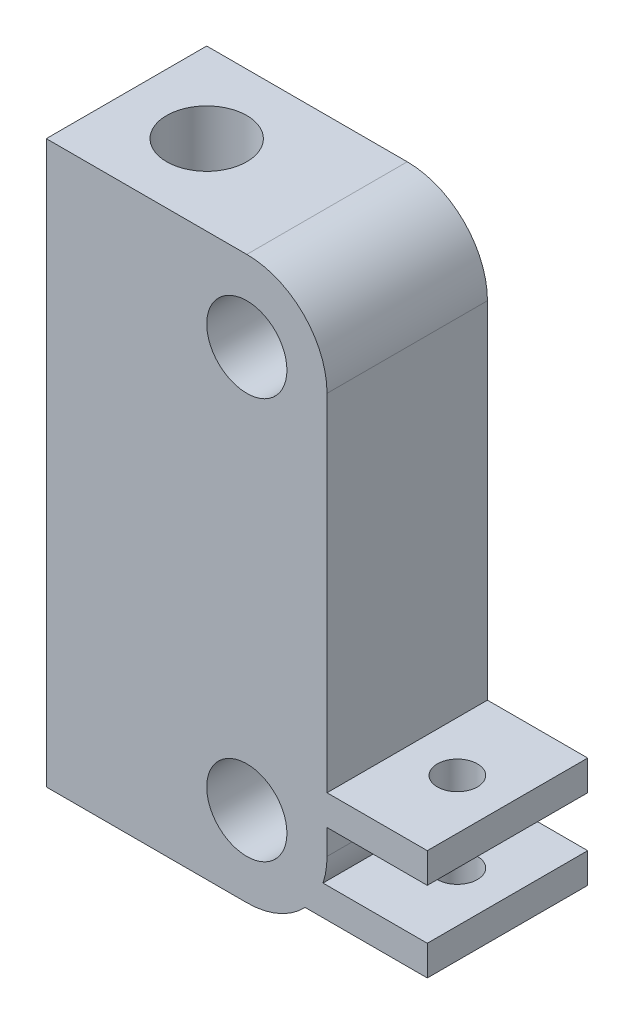
SolidWorks part; units mm, degrees
material "ABS"
ref_plane "Front Plane" through (0, 0, 0) normal (0, 0, 1) x (1, 0, 0)
ref_plane "Top Plane" through (0, 0, 0) normal (0, 1, 0) x (1, 0, 0)
ref_plane "Right Plane" through (0, 0, 0) normal (1, 0, 0) x (0, 0, -1)
sketch "Sketch1" plane through (0, 0, 0) normal (0, 0, 1) x (1, 0, 0)
  line L0 (11.942, -20.8688) -> (21.942, -20.8688)
  line L1 (-16.058, 21.6312) -> (3.942, 21.6312)
  line L2 (-16.058, 21.6312) -> (-16.058, -34.3688)
  line L3 (-16.058, -34.3688) -> (3.942, -34.3688)
  line L4 (11.942, 13.6312) -> (11.942, -20.8688)
  line L5 (21.942, -20.8688) -> (21.942, -23.8688)
  line L6 (21.942, -23.8688) -> (11.942, -23.8688)
  line L7 (9.7514, -31.8688) -> (21.942, -31.8688)
  line L8 (21.942, -31.8688) -> (21.942, -28.8688)
  line L9 (21.942, -28.8688) -> (11.5413, -28.8688)
  line L10 (11.942, -23.8688) -> (11.942, -26.3688)
  circle A0 centre (3.942, 13.6312) radius 4
  circle A1 centre (3.942, -26.3688) radius 4
  arc A2 (3.942, -34.3688) -> (9.7514, -31.8688) centre (3.942, -26.3688) ccw
  arc A3 (3.942, 21.6312) -> (11.942, 13.6312) centre (3.942, 13.6312) cw
  arc A4 (11.5413, -28.8688) -> (11.942, -26.3688) centre (3.942, -26.3688) ccw
  dimension "D1" = 8
  dimension "D2" = 8
  dimension "D8" = 8
  dimension "D3" = 40
  dimension "D4" = 8
  dimension "D5" = 8
  dimension "D6" = 8
  dimension "D7" = 8
  dimension "D9" = 28
  dimension "D10" = 3
  dimension "D11" = 3
  dimension "D12" = 2.5
  dimension "D13" = 5
  dimension "D14" = 10
extrude "Boss-Extrude1" add sketch "Sketch1" against normal blind 16
sketch "Sketch2" plane through (0, 21.6312, 0) normal (0, 1, 0) x (1, 0, 0)
  line L0 (3.942, 0) -> (-16.058, 0) construction
  line L1 (-16.058, 16) -> (-16.058, 0) construction
  circle A0 centre (-8.058, 8) radius 4
  dimension "D1" = 8
  dimension "D2" = 8
  dimension "D3" = 8
extrude "Cut-Extrude1" cut sketch "Sketch2" against normal through all
ref_point "Point1"
sketch "Sketch3" plane through (0, -20.8688, 0) normal (0, 1, 0) x (1, 0, 0)
  line L0 (21.942, 16) -> (21.942, 0) construction
  line L2 (21.942, 16) -> (11.942, 16) construction
  circle A0 centre (16.942, 8) radius 2
  dimension "D1" = 4
  dimension "D2" = 5
  dimension "D3" = 8
extrude "Cut-Extrude2" cut sketch "Sketch3" against normal through all
equation "\"rod_diameter\"= 8"
equation "\"rod_hole_thickness\"= 4"
equation "\"D1@Sketch1\"=\"rod_diameter\""
equation "\"D2@Sketch1\"=\"rod_diameter\""
equation "\"rod_radius\"= \"rod_diameter\" / 2"
equation "\"D4@Sketch1\"=\"rod_radius\"+\"rod_hole_thickness\""
equation "\"D5@Sketch1\"=\"rod_radius\"+\"rod_hole_thickness\""
equation "\"D6@Sketch1\"=\"rod_radius\"+\"rod_hole_thickness\""
equation "\"D7@Sketch1\"=\"rod_radius\"+\"rod_hole_thickness\""
equation "\"D8@Sketch1\"=\"rod_radius\"+\"rod_hole_thickness\""
equation "\"D9@Sketch1\"=\"rod_diameter\"*2 + \"rod_hole_thickness\"*3"
equation "\"D1@Boss-Extrude1\"= \"rod_diameter\" + \"rod_hole_thickness\" * 2"
equation "\"D1@Sketch2\"=\"rod_diameter\""
equation "\"D2@Sketch2\"=\"rod_radius\"+\"rod_hole_thickness\""
equation "\"D3@Sketch2\" = \"rod_radius\" + \"rod_hole_thickness\""
equation "\"platter_diameter\"= 320"
equation "\"platter_radius\"= \"platter_diameter\" / 2"
equation "\"extruder_mount_hole_spacing\"= 75"
equation "\"arm_rod_spacing\"= 40"
equation "\"D3@Sketch1\"=\"arm_rod_spacing\""
equation "\"D2@Sketch3\" = \"D14@Sketch1\" / 2"
equation "\"D3@Sketch3\"= \"D1@Boss-Extrude1\" / 2"
equation "\"top_frame_spacing\"= 90"
equation "\"motor_level_rod_spacing\"= 15"
equation "\"linear_bearing_diameter\"= 15"
equation "\"z_rod_spacing\"= 75"
equation "\"z_drive_rod_offset\"= 12"
equation "\"platter_rod_spacing\"= 50"
equation "\"rod_nut_thickness\"= 6.5"
equation "\"rod_nut_inscribed_diameter\"= 13"
equation "\"z_height\"= 400"
equation "\"gear_pitch\"=2"
equation "\"r_gear_teeth\"= 450"
equation "\"theta_gear_teeth\"= 385"
equation "\"sheet_thickness\"=5.333"
equation "\"sheet_tab_hole_thickness\"= \"sheet_thickness\""
equation "\"sheet_tab_width\"= \"sheet_thickness\"*2"
equation "\"sheet_double_tab_width\"= 35"
equation "\"sheet_bolt_diameter\"= 3"
equation "\"sheet_bolt_length\"= 16"
equation "\"sheet_nut_diameter\"= 5.5"
equation "\"sheet_nut_thickness\"= 2.5"
equation "\"sheet_nut_depth\"= 10"
equation "\"bearing_outside_diameter\"= 22"
equation "\"bearing_thickness\"= 7"
equation "\"corner_part_thickness\"= \"sheet_thickness\" + \"bearing_thickness\""
equation "\"setscrew_nut_diameter\"= 6"
equation "\"setscrew_nut_thickness\"= 3"
equation "\"setscrew_bolt_diameter\"= 3"
equation "\"motor_shaft_diameter\"= 5.7"
equation "\"printed_hole_tolerance\"= 1"
equation "\"D1@Sketch3\"=\"sheet_bolt_diameter\"+\"printed_hole_tolerance\""
